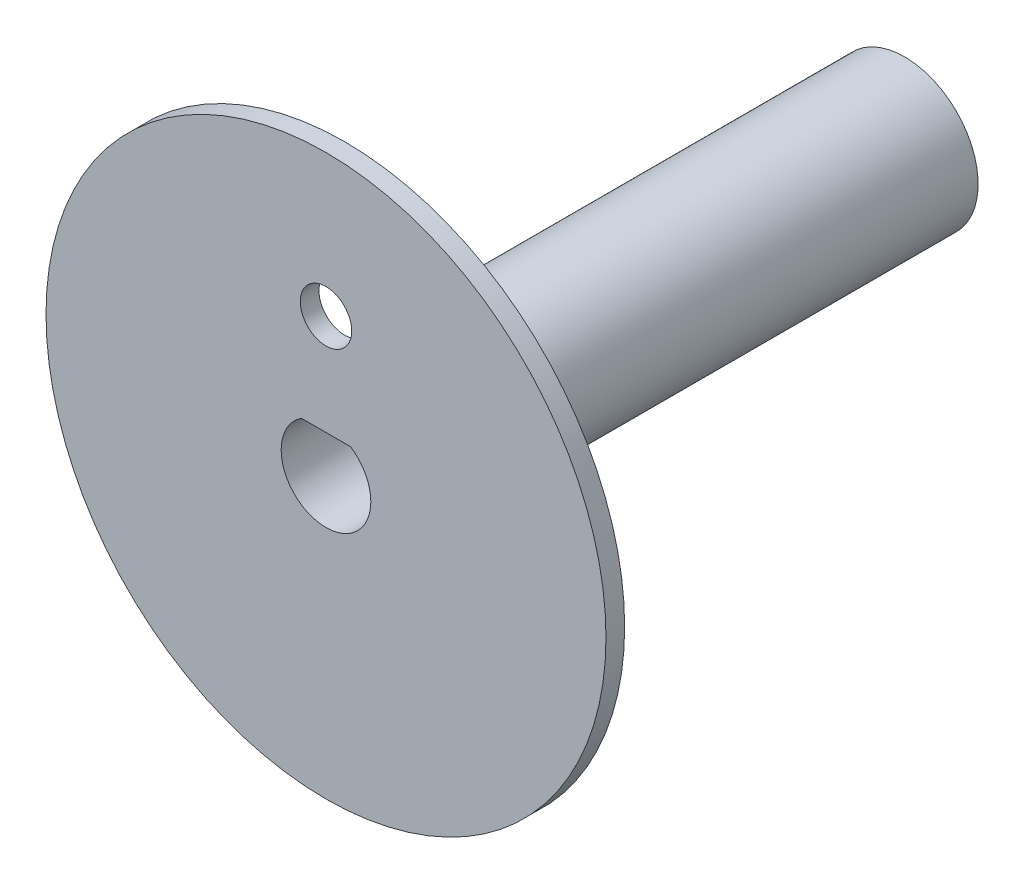
SolidWorks part; units mm, degrees
ref_plane "Front Plane" through (0, 0, 0) normal (0, 0, 1) x (1, 0, 0)
ref_plane "Top Plane" through (0, 0, 0) normal (0, 1, 0) x (1, 0, 0)
ref_plane "Right Plane" through (0, 0, 0) normal (1, 0, 0) x (0, 0, -1)
sketch "Sketch1" plane through (0, 0, 0) normal (0, 0, 1) x (1, 0, 0)
  circle A0 centre (0, 0) radius 5
  dimension "D1" = 10
extrude "Boss-Extrude1" add sketch "Sketch1" along normal blind 38.1
sketch "Sketch2" plane through (0, 0, 38.1) normal (0, 0, 1) x (1, 0, 0)
  circle A0 centre (0, 0) radius 19.05
  dimension "D1" = 38.1
extrude "Boss-Extrude2" add sketch "Sketch2" along normal blind 1.27
sketch "Sketch3" plane through (0, 0, 0) normal (0, 0, -1) x (-1, 0, 0)
  circle A0 centre (0, 0) radius 3.05
  dimension "D1" = 6.1
extrude "Cut-Extrude1" cut sketch "Sketch3" against normal through all
sketch "Sketch4" plane through (0, 0, 38.1) normal (0, 0, -1) x (-1, 0, 0)
  circle A0 centre (0, 9.398) radius 1.75
  circle A1 centre (0, 0) radius 19.05 construction
  dimension "D1" = 3.5
  dimension "D2" = 9.398
extrude "Cut-Extrude2" cut sketch "Sketch4" against normal blind 7.62
sketch "Sketch5" plane through (0, 0, 39.37) normal (0, 0, 1) x (1, 0, 0)
  line L0 (-1.6733, 2.55) -> (1.6733, 2.55)
  circle A0 centre (0, 0) radius 3.05 construction
  arc A1 (-1.6733, 2.55) -> (1.6733, 2.55) centre (0, 0) cw
  point P4 (0, -3.05)
  point P6 (0, 0.5996)
  point P8 (0, 0)
  dimension "D1" = 5.6
extrude "Boss-Extrude3" add sketch "Sketch5" against normal through all
